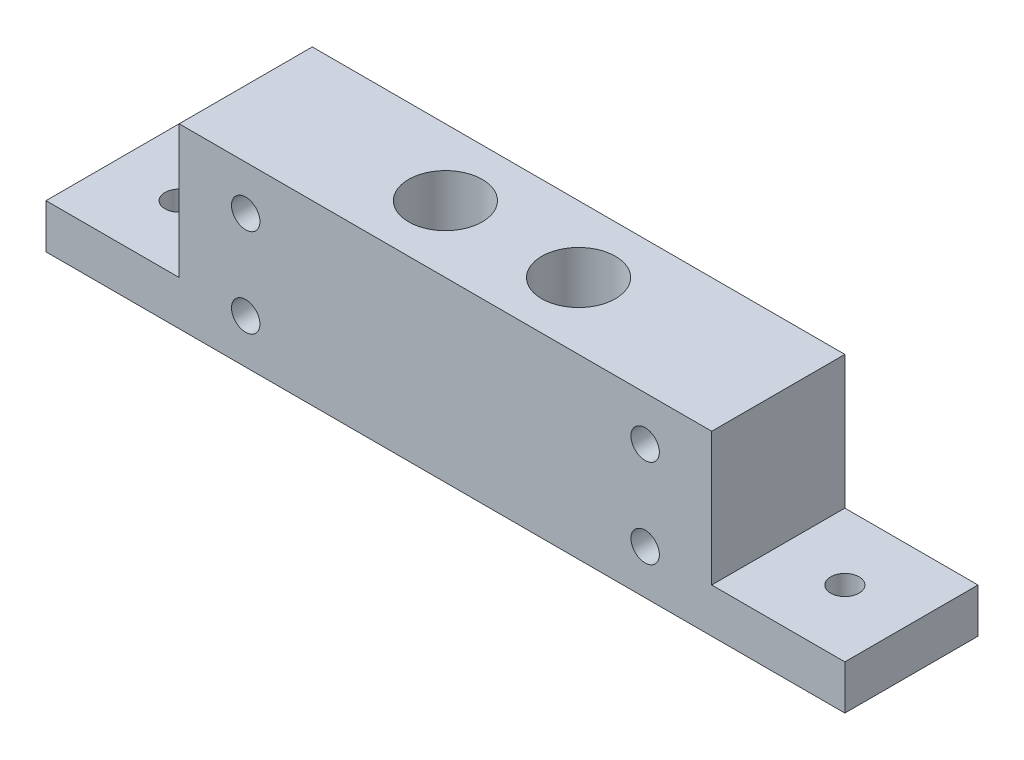
SolidWorks part; units mm, degrees
ref_plane "Front Plane" through (0, 0, 0) normal (0, 0, 1) x (1, 0, 0)
ref_plane "Top Plane" through (0, 0, 0) normal (0, 1, 0) x (1, 0, 0)
ref_plane "Right Plane" through (0, 0, 0) normal (1, 0, 0) x (0, 0, -1)
sketch "Sketch2" plane through (0, 0, 0) normal (0, 1, 0) x (1, 0, 0)
  line L0 (0, 0) -> (-7.5, 0) construction
  line L1 (0, 0) -> (7.5, 0) construction
  line L3 (15, -7.5) -> (-15, -7.5)
  line L4 (15, -7.5) -> (15, 7.5)
  line L5 (15, 7.5) -> (-15, 7.5)
  line L6 (-15, -7.5) -> (-15, 7.5)
  line L7 (15, -7.5) -> (-15, 7.5) construction
  line L8 (15, 7.5) -> (-15, -7.5) construction
  line L9 (-15, 7.5) -> (-30, 7.5)
  line L10 (-15, 7.5) -> (-15, -7.5)
  line L11 (-15, -7.5) -> (-30, -7.5)
  line L12 (-30, 7.5) -> (-30, -7.5)
  line L13 (15, 7.5) -> (30, 7.5)
  line L14 (15, 7.5) -> (15, -7.5)
  line L15 (15, -7.5) -> (30, -7.5)
  line L16 (30, 7.5) -> (30, -7.5)
  circle A0 centre (-7.5, 0) radius 4.15
  circle A1 centre (7.5, 0) radius 4.15
  dimension "D3" = 8.3
  dimension "D4" = 8.3
  dimension "D1" = 7.5
  dimension "D2" = 7.5
  dimension "D5" = 15
  dimension "D6" = 30
  dimension "D7" = 15
  dimension "D8" = 15
  dimension "D9" = 15
  dimension "D10" = 15
extrude "Boss-Extrude1" add sketch "Sketch2" along normal blind 10 contours L9 L12 L11 L6 | L6 L3 L4 L5 A1 A0 | L16 L13 L4 L15 region at (0, 0, 0) region at (22.5, 0, 0) region at (-22.5, 0, 0)
extrude "Boss-Extrude2" add sketch "Sketch2<3>" against normal blind 10 contours L9 L12 L11 L6 | L6 L3 L4 L5 A1 A0 | A0 | A1 | L16 L13 L4 L15 region at (0, 0, 0) region at (22.5, 0, 0) region at (-22.5, 0, 0) region at (-7.5, 0, 0) region at (7.5, 0, 0)
sketch "Sketch2<3>" plane through (0, 0, 0) normal (0, 1, 0) x (1, 0, 0) same geometry as "Sketch2"
sketch "Sketch4" plane through (0, 0, 7.5) normal (0, 0, 1) x (1, 0, 0)
  line L0 (-30, 0) -> (-22.5, 0) construction
  line L1 (-30, 10) -> (-30, -10) construction
  line L2 (30, 0) -> (22.5, 0) construction
  line L3 (30, 10) -> (30, -10) construction
  line L4 (-22.5, -5) -> (-22.5, 5) construction
  line L5 (22.5, -5) -> (22.5, 5) construction
  line L7 (-22.5, 8.4352) -> (-25.475, 6.7176)
  line L8 (-25.475, 6.7176) -> (-25.475, 3.2824)
  line L9 (-25.475, 3.2824) -> (-22.5, 1.5648)
  line L10 (-22.5, 1.5648) -> (-19.525, 3.2824)
  line L11 (-19.525, 3.2824) -> (-19.525, 6.7176)
  line L12 (-19.525, 6.7176) -> (-22.5, 8.4352)
  line L13 (22.5, 8.4352) -> (19.525, 6.7176)
  line L14 (19.525, 6.7176) -> (19.525, 3.2824)
  line L15 (19.525, 3.2824) -> (22.5, 1.5648)
  line L16 (22.5, 1.5648) -> (25.475, 3.2824)
  line L17 (25.475, 3.2824) -> (25.475, 6.7176)
  line L18 (25.475, 6.7176) -> (22.5, 8.4352)
  line L19 (-22.5, -8.4352) -> (-19.525, -6.7176)
  line L20 (22.5, -8.4352) -> (25.475, -6.7176)
  line L21 (25.475, -6.7176) -> (25.475, -3.2824)
  line L22 (25.475, -3.2824) -> (22.5, -1.5648)
  line L23 (22.5, -1.5648) -> (19.525, -3.2824)
  line L24 (19.525, -3.2824) -> (19.525, -6.7176)
  line L25 (19.525, -6.7176) -> (22.5, -8.4352)
  line L26 (-19.525, -6.7176) -> (-19.525, -3.2824)
  line L27 (-19.525, -3.2824) -> (-22.5, -1.5648)
  line L28 (-22.5, -1.5648) -> (-25.475, -3.2824)
  line L29 (-25.475, -3.2824) -> (-25.475, -6.7176)
  line L30 (-25.475, -6.7176) -> (-22.5, -8.4352)
  circle A0 centre (22.5, 5) radius 1.6
  circle A1 centre (22.5, -5) radius 1.6
  circle A2 centre (-22.5, -5) radius 1.6
  circle A3 centre (-22.5, 5) radius 1.6
  circle A4 centre (-22.5, 5) radius 2.975 construction
  circle A5 centre (22.5, 5) radius 2.975 construction
  circle A6 centre (22.5, -5) radius 2.975 construction
  circle A7 centre (-22.5, -5) radius 2.975 construction
  point P12 (-22.5, 0)
  point P15 (22.5, 0)
  dimension "D5" = 3.2
  dimension "D6" = 3.2
  dimension "D7" = 3.2
  dimension "D8" = 3.2
  dimension "D9" = 5.95
  dimension "D10" = 5.95
  dimension "D11" = 5.95
  dimension "D12" = 5.95
  dimension "D1" = 7.5
  dimension "D2" = 7.5
  dimension "D3" = 10
  dimension "D4" = 10
extrude "Cut-Extrude1" cut sketch "Sketch4" against normal through all contours A2 | A3 | A0 | A1 region at (22.5, 5, 7.5) region at (22.5, -5, 7.5) region at (-22.5, -5, 7.5) region at (-22.5, 5, 7.5)
extrude "Cut-Extrude2" cut sketch "Sketch4<3>" against normal blind 2.5 from offset 6.25 offset against normal yes
sketch "Sketch4<3>" plane through (0, 0, 7.5) normal (0, 0, 1) x (1, 0, 0) same geometry as "Sketch4"
sketch "Sketch5" plane through (0, -10, 0) normal (0, -1, 0) x (1, 0, 0)
  line L1 (-30, 7.5) -> (-45, 7.5)
  line L2 (-30, 7.5) -> (-30, -7.5)
  line L3 (-30, -7.5) -> (-45, -7.5)
  line L4 (-45, 7.5) -> (-45, -7.5)
  line L5 (30, 7.5) -> (45, 7.5)
  line L6 (30, 7.5) -> (30, -7.5)
  line L7 (30, -7.5) -> (45, -7.5)
  line L8 (45, 7.5) -> (45, -7.5)
  dimension "D1" = 15
  dimension "D2" = 15
extrude "Boss-Extrude3" add sketch "Sketch5" against normal blind 5
sketch "Sketch6" plane through (0, -10, 0) normal (0, -1, 0) x (1, 0, 0)
  line L0 (-45, 7.5) -> (-30, -7.5) construction
  line L1 (45, -7.5) -> (-45, -7.5) construction
  line L2 (0, 0) -> (0, 7.5) construction
  line L3 (45, 7.5) -> (-45, 7.5) construction
  circle A0 centre (-37.5, 0) radius 1.6
  circle A1 centre (37.5, 0) radius 1.6
  dimension "D1" = 3.2
extrude "Cut-Extrude3" cut sketch "Sketch6" against normal up to next
sketch "Sketch7" plane through (0, 0, 0) normal (0, 1, 0) x (1, 0, 0)
  circle A0 centre (-7.5, 0) radius 4.15
  circle A1 centre (7.5, 0) radius 4.15
extrude "Cut-Extrude4" cut sketch "Sketch7" against normal blind 8
